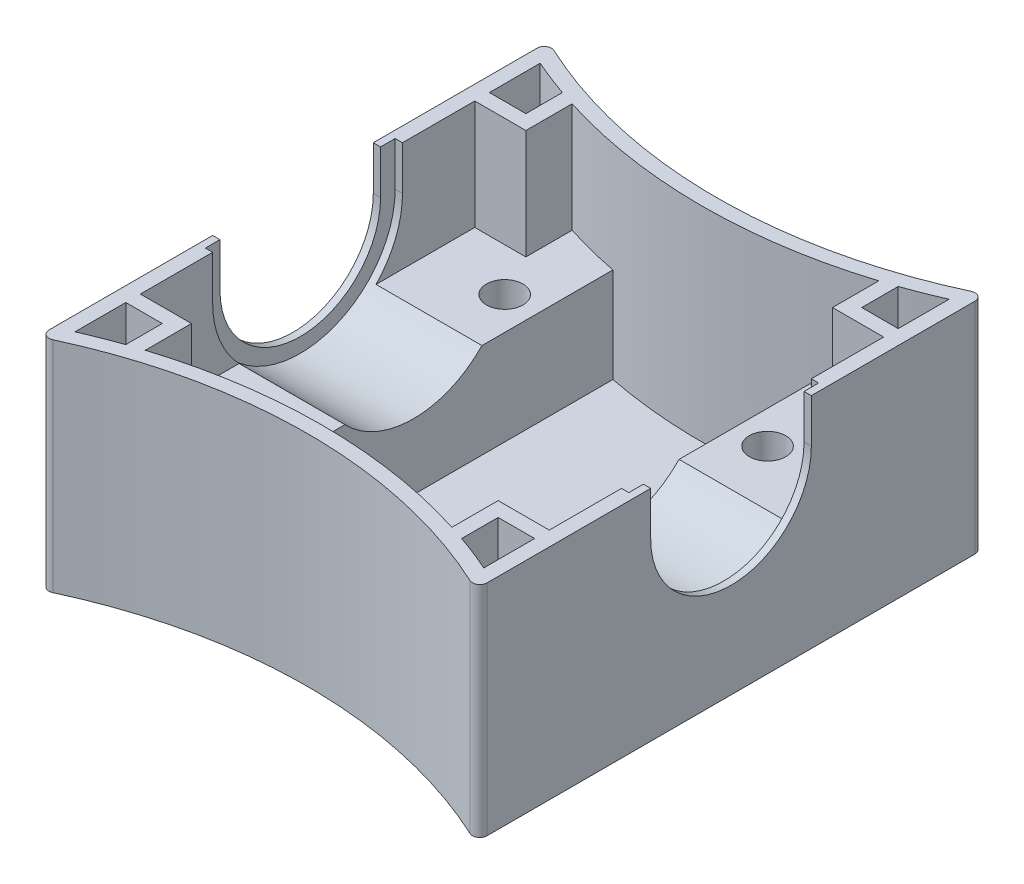
SolidWorks part; units mm, degrees
ref_plane "Plano frontal" through (0, 0, 0) normal (0, 0, 1) x (1, 0, 0)
ref_plane "Plano superior" through (0, 0, 0) normal (0, 1, 0) x (1, 0, 0)
ref_plane "Plano direito" through (0, 0, 0) normal (1, 0, 0) x (0, 0, -1)
sketch "Esboço2" plane through (0, 0, 0) normal (0, 1, 0) x (1, 0, 0)
  line L1 (-30, 35) -> (30, 35) construction
  line L2 (-30, 35) -> (-30, -35)
  line L3 (-30, -35) -> (30, -35) construction
  line L4 (30, 35) -> (30, -35)
  line L5 (-30, 35) -> (30, -35) construction
  line L6 (-30, -35) -> (30, 35) construction
  line L7 (-35.8677, 28) -> (35.8677, 28) construction
  line L8 (-37.175, -28) -> (37.175, -28) construction
  arc A0 (-30, 35) -> (30, 35) centre (0, 95.7857) ccw
  arc A1 (-30, -35) -> (30, -35) centre (0, -95.7857) cw
  point P0 (0, 0)
  point P10 (0, 28)
  point P15 (0, -28)
  dimension "D3" = 7
  dimension "D1" = 60
  dimension "D2" = 70
  dimension "D4" = 7
extrude "Ressalto-extrusão2" add sketch "Esboço2" along normal blind 30
shell "Casca1" thickness 2 removed face at (0, 30, 0)
sketch "Esboço5" plane through (0, 2, 0) normal (0, 1, 0) x (1, 0, 0)
  line L0 (28, -31.8635) -> (28, 31.8635) construction
  line L1 (28, 24.8991) -> (23, 24.8991)
  line L2 (28, 24.8991) -> (28, 29.8991)
  line L3 (28, 29.8991) -> (23, 29.8991)
  line L4 (23, 24.8991) -> (23, 29.8991)
  line L5 (-28, -24.8991) -> (-23, -24.8991)
  line L6 (28, 29.8991) -> (21, 29.8991)
  line L7 (28, 29.8991) -> (28, 22.8991)
  line L8 (28, 22.8991) -> (21, 22.8991)
  line L9 (21, 29.8991) -> (21, 22.8991)
  line L10 (-23, -24.8991) -> (-23, -29.8991)
  line L11 (-21, -29.8991) -> (-21, -22.8991)
  line L12 (-28, -22.8991) -> (-21, -22.8991)
  line L13 (23, -24.8991) -> (28, -24.8991)
  line L14 (23, -24.8991) -> (23, -29.8991)
  line L15 (21, -29.2346) -> (21, -22.8991)
  line L16 (21, -22.8991) -> (28, -22.8991)
  line L17 (-21, 22.8991) -> (-28, 22.8991)
  line L18 (-21, 29.2346) -> (-21, 22.8991)
  line L19 (-23, 24.8991) -> (-23, 29.8991)
  line L20 (-23, 24.8991) -> (-28, 24.8991)
  arc A0 (-28, 31.8635) -> (28, 31.8635) centre (0, 95.7857) ccw construction
  arc A1 (28, -31.8635) -> (-28, -31.8635) centre (0, -95.7857) ccw construction
  point P20 (0, 0)
  point P36 (0, 0)
  arc M5 (-28, -31.8635) -> (28, -31.8635) centre (0, -95.7857) cw
  line M6 (28, -31.8635) -> (28, 31.8635)
  arc M7 (28, 31.8635) -> (-28, 31.8635) centre (0, 95.7857) cw
  line M8 (-28, 31.8635) -> (-28, -31.8635)
  dimension "D1" = 5
  dimension "D2" = 5
  dimension "D3" = 7
  dimension "D4" = 7
  dimension "D5" = 2
  dimension "D6" = 2
extrude "Ressalto-extrusão3" add sketch "Esboço5" along normal blind 28 contours L9 L8 L1 L4 M7 M6 | L12 L5 L10 L11 M8 M5 | L19 L20 L17 L18 M8 M7 | L16 L15 L14 L13 M5 M6 region at (27.901, 2, -23.8991) region at (27.901, 2, 23.8991) region at (-21.099, 2, -26.0669) region at (-22.0337, 2, 29.4654)
sketch "Esboço6" plane through (0, 2, 0) normal (0, 1, 0) x (1, 0, 0)
  line L0 (0, 66.0228) -> (0, -66.0228) construction
  line L2 (-15.5, -27.7431) -> (15.5, -27.7431)
  line L3 (-15.5, -27.7431) -> (-15.5, 27.7431)
  line L4 (-15.5, 27.7431) -> (15.5, 27.7431)
  line L5 (15.5, -27.7431) -> (15.5, 27.7431)
  line L6 (-15.5, -27.7431) -> (15.5, 27.7431) construction
  line L7 (-15.5, 27.7431) -> (15.5, -27.7431) construction
  arc A0 (-21, 29.2346) -> (21, 29.2346) centre (0, 95.7857) ccw construction
  point P0 (0, 0)
  point P4 (0, 0)
  arc M8 (21, 29.2346) -> (-21, 29.2346) centre (0, 95.7857) cw
  arc M14 (-21, -29.2346) -> (21, -29.2346) centre (0, -95.7857) cw
  dimension "D1" = 31
extrude "Ressalto-extrusão4" add sketch "Esboço6" along normal blind 13 contours L5 L3 M14 M8 region at (0, 2, 0)
shell "Casca2" thickness 2 removed face at (0, 15, 0)
sketch "Esboço9" plane through (-30, 0, 0) normal (-1, 0, 0) x (0, 0, 1)
  line L0 (-35, 0) -> (35, 0) construction
  line L1 (-13, 24) -> (-13, 44)
  line L2 (13, 24) -> (13, 44)
  line L3 (13, 44) -> (-13, 44)
  circle A0 centre (0, 24) radius 13
  point P2 (0, 0)
  point P5 (13, 24)
  point P6 (-13, 24)
  line M3 (35, 30) -> (-35, 30)
  dimension "D1" = 26
  dimension "D2" = 24
sketch "Esboço12" plane through (0, 2, 0) normal (0, 1, 0) x (1, 0, 0)
  point P0 (21.3527, -1.9795)
  line M1 (15.5, 27.7431) -> (15.5, -27.7431)
  arc M2 (15.5, -27.7431) -> (21, -29.2346) centre (0, -95.7857) cw
  line M3 (21, -29.2346) -> (21, -22.8991)
  line M4 (21, -22.8991) -> (28, -22.8991)
  line M5 (28, -22.8991) -> (28, 22.8991)
  line M6 (28, 22.8991) -> (21, 22.8991)
  line M7 (21, 22.8991) -> (21, 29.2346)
  arc M8 (21, 29.2346) -> (15.5, 27.7431) centre (0, 95.7857) cw
extrude "Ressalto-extrusão5" add sketch "Esboço12" along normal blind 13 contours M8 M1 M2 M3 M4 M5 M6 M7 region at (21.4246, 2, 0)
sketch "Esboço13" plane through (0, 2, 0) normal (0, 1, 0) x (1, 0, 0)
  point P0 (-20.6439, -8.062)
  arc M1 (-21, -29.2346) -> (-15.5, -27.7431) centre (0, -95.7857) cw
  line M2 (-15.5, -27.7431) -> (-15.5, 27.7431)
  arc M3 (-15.5, 27.7431) -> (-21, 29.2346) centre (0, 95.7857) cw
  line M4 (-21, 29.2346) -> (-21, 22.8991)
  line M5 (-21, 22.8991) -> (-28, 22.8991)
  line M6 (-28, 22.8991) -> (-28, -22.8991)
  line M7 (-28, -22.8991) -> (-21, -22.8991)
  line M8 (-21, -22.8991) -> (-21, -29.2346)
extrude "Ressalto-extrusão6" add sketch "Esboço13" along normal blind 13 contours M8 M1 M2 M3 M4 M5 M6 M7 region at (-21.4246, 2, 0)
extrude "Corte-extrusão1" cut sketch "Esboço9" against normal blind 60 contours A0 M3 | A0 L2 L3 L1 M3 | A0 L2 M3 | A0 L1 M3 | A0 M3 region at (-30, 21.5404, 0) region at (-30, 28.5175, -12.5644) region at (-30, 38.9091, 0) region at (-30, 28.5175, 12.5644) region at (-30, 32.8767, 0)
sketch "Esboço14" plane through (-30, 0, 0) normal (-1, 0, 0) x (0, 0, 1)
  line L0 (-13, 24) -> (13, 24)
  arc A0 (-13, 24) -> (13, 24) centre (0, 24) ccw
extrude "Ressalto-extrusão7" add sketch "Esboço14" against normal blind 1
sketch "Esboço15" plane through (30, 0, 0) normal (1, 0, 0) x (0, 0, -1)
  line L0 (-13, 24) -> (13, 24)
  arc A0 (-13, 24) -> (13, 24) centre (0, 24) ccw
extrude "Ressalto-extrusão8" add sketch "Esboço15" against normal blind 1
sketch "Esboço16" plane through (-30, 0, 0) normal (-1, 0, 0) x (0, 0, 1)
  circle A0 centre (0, 24) radius 11
extrude "Corte-extrusão2" cut sketch "Esboço16" against normal blind 60
sketch "Esboço17" plane through (0, 15, 0) normal (0, 1, 0) x (1, 0, 0)
  line L0 (13.5, 9.3808) -> (13.5, 27.3182) construction
  circle A0 centre (18, 17) radius 2.5
  circle A1 centre (-18, -17) radius 2.5
  circle A2 centre (18, -17) radius 2.5
  circle A3 centre (-18, 17) radius 2.5
  point P8 (0, 0)
  dimension "D1" = 4.5
  dimension "D2" = 4
  dimension "D3" = 2
extrude "Corte-extrusão3" cut sketch "Esboço17" against normal up to surface (15 mm away) up to face at (0, 0, 0)
fillet "Filete1" radius 1 4 edges at (-30, 15, -35) (30, 15, -35) (30, 15, 35) (-30, 15, 35)
sketch "Esboço18" plane through (0, 24, 0) normal (0, 1, 0) x (1, 0, 0)
  line L0 (-29, -13) -> (-29, -11) construction
  line L1 (-30, 13) -> (-29, 13)
  line L2 (-30, 13) -> (-30, 11)
  line L3 (-30, 11) -> (-29, 11)
  line L4 (-29, 13) -> (-29, 11)
  line L5 (-30, -11) -> (-29, -11)
  line L6 (-30, -11) -> (-30, -13)
  line L7 (-30, -13) -> (-29, -13)
  line L8 (-29, -11) -> (-29, -13)
  line L9 (30, 11) -> (29, 11) construction
  line L10 (30, 13) -> (29, 13)
  line L11 (30, 13) -> (30, 11)
  line L12 (30, 11) -> (29, 11)
  line L13 (29, 13) -> (29, 11)
  line L14 (29, 13) -> (29, 11) construction
  line L15 (30, -11) -> (30, -13) construction
  line L16 (29, -11) -> (30, -11)
  line L17 (29, -11) -> (29, -13)
  line L18 (29, -13) -> (30, -13)
  line L19 (30, -11) -> (30, -13)
extrude "Ressalto-extrusão9" add sketch "Esboço18" along normal up to surface (6 mm away) up to face at (25.5047, 30, -27.8782)
